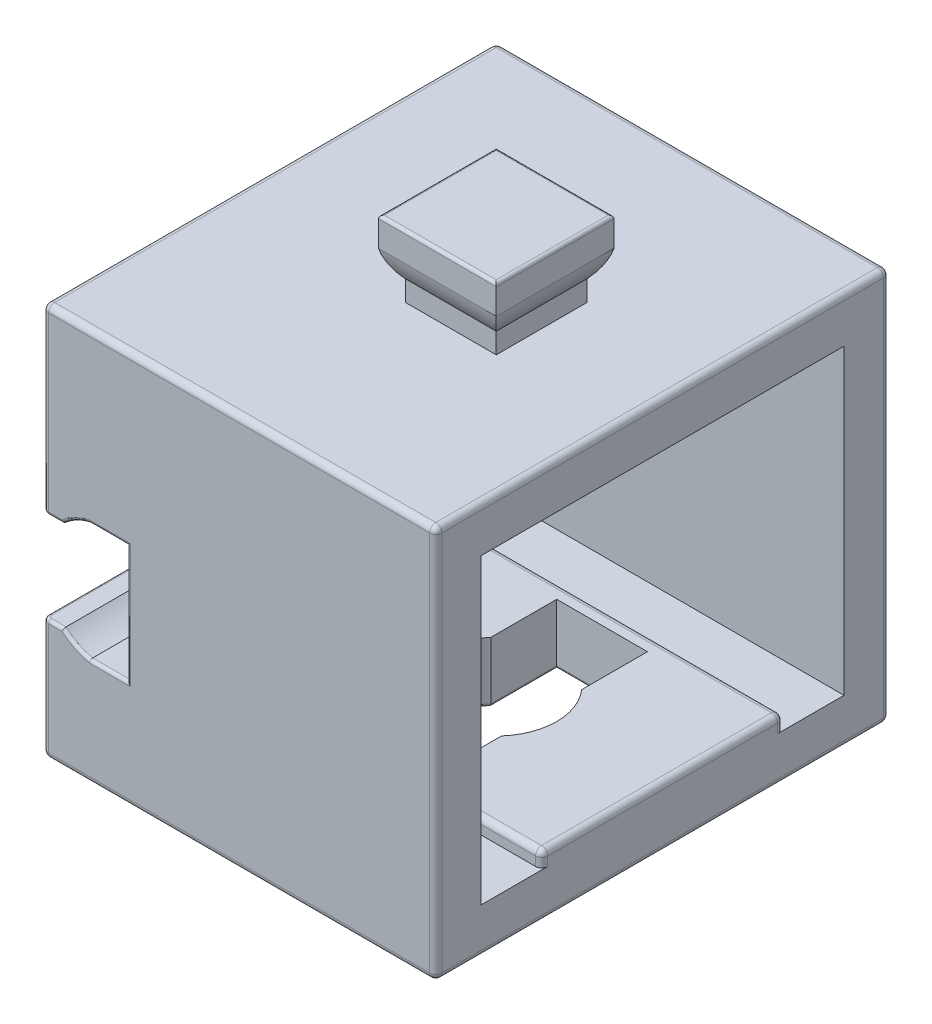
SolidWorks part; units mm, degrees
ref_plane "前视基准面" through (0, 0, 0) normal (0, 0, 1) x (1, 0, 0)
ref_plane "上视基准面" through (0, 0, 0) normal (0, 1, 0) x (1, 0, 0)
ref_plane "右视基准面" through (0, 0, 0) normal (1, 0, 0) x (0, 0, -1)
sketch "草图1" plane through (0, 0, 0) normal (0, 1, 0) x (1, 0, 0)
  line L0 (-6.5, 7.5) -> (-6.5, -7.5)
  line L1 (-6.5, 7.5) -> (6.5, 7.5)
  line L2 (-6.5, -7.5) -> (6.5, -7.5)
  line L3 (6.5, 7.5) -> (6.5, -7.5)
  line L4 (-6.5, 7.5) -> (6.5, -7.5) construction
  line L5 (-6.5, -7.5) -> (6.5, 7.5) construction
  point P1 (0, 0)
  dimension "D1" = 13
  dimension "D2" = 15
extrude "凸台-拉伸1" add sketch "草图1" along normal blind 13
sketch "草图2" plane through (6.5, 0, 0) normal (1, 0, 0) x (0, 0, -1)
  line L0 (-7.5, 13) -> (7.5, 13) construction
  line L1 (-6, 11.5) -> (6, 11.5)
  line L2 (-6, 11.5) -> (-6, 1.5)
  line L3 (-4, 1.5) -> (-6, 1.5)
  line L4 (6, 11.5) -> (6, 1.5)
  line L5 (-7.5, 13) -> (-7.5, 0) construction
  line L6 (7.5, 13) -> (7.5, 0) construction
  line L8 (-4, 2) -> (4, 2)
  line L9 (-4, 2) -> (-4, 1.5)
  line L10 (4, 1.5) -> (6, 1.5)
  line L11 (4, 2) -> (4, 1.5)
  dimension "D1" = 1.5
  dimension "D2" = 1.5
  dimension "D3" = 1.5
  dimension "D4" = 0.5
  dimension "D5" = 4
  dimension "D6" = 8
  dimension "D7" = 2
  dimension "D8" = 0.5
extrude "切除-拉伸1" cut sketch "草图2" against normal blind 11.5
sketch "草图3" plane through (-5, 0, 0) normal (1, 0, 0) x (0, 0, -1)
  line L0 (0, 0) -> (0, 5.5) construction
  line L1 (-7.5, 0) -> (7.5, 0) construction
  line L2 (0, 5.5) -> (-6, 5.5) construction
  line L3 (-6, 11.5) -> (-6, 1.5) construction
  line L4 (0, 5.5) -> (2.5, 5.5) construction
  line L5 (0, 8.5) -> (2.5, 8.5)
  line L6 (0, 8.5) -> (-6, 8.5)
  line L7 (0, 2.5) -> (2.5, 2.5)
  line L8 (0, 2.5) -> (-6, 2.5)
  line L9 (-6, 8.5) -> (-6, 2.5)
  line L10 (2.5, 8.5) -> (2.5, 2.5)
  dimension "D1" = 5.5
  dimension "D2" = 6
  dimension "D3" = 2.5
  dimension "D4" = 3
  dimension "D5" = 3
extrude "凸台-拉伸2" add sketch "草图3" along normal blind 1.5
sketch "草图4" plane through (0, 0, 0) normal (0, -1, 0) x (1, 0, 0)
  line L0 (6.5, 0) -> (1, 0) construction
  line L1 (6.5, 7.5) -> (6.5, -7.5) construction
  line L3 (2.5, 3.5) -> (-0.5, 3.5)
  line L4 (2.5, 3.5) -> (2.5, 1.3229)
  line L5 (-0.5, 3.5) -> (-0.5, 1.3229)
  line L6 (2.5, -3.5) -> (-0.5, -3.5)
  line L7 (2.5, 3.5) -> (-0.5, -3.5) construction
  line L8 (-0.5, 3.5) -> (2.5, -3.5) construction
  line L9 (-0.5, -1.3229) -> (-0.5, -3.5)
  line L10 (2.5, -1.3229) -> (2.5, -3.5)
  arc A0 (-0.5, 1.3229) -> (-0.5, -1.3229) centre (1, 0) ccw
  arc A1 (2.5, -1.3229) -> (2.5, 1.3229) centre (1, 0) ccw
  dimension "D2" = 4
  dimension "D1" = 5.5
  dimension "D3" = 3
  dimension "D4" = 7
extrude "切除-拉伸2" cut sketch "草图4" against normal up to next
sketch "草图5" plane through (0, 0, 7.5) normal (0, 0, 1) x (1, 0, 0)
  line L0 (-6.5, 13) -> (-6.5, 5.5) construction
  line L1 (-6.5, 13) -> (-6.5, 0) construction
  line L2 (-6.5, 5.5) -> (-4.5, 5.5) construction
  line L3 (-4.5, 5.5) -> (-3.7, 5.5) construction
  line L4 (-6.5, 4) -> (-6.5, 7)
  line L5 (-6.5, 7) -> (-5.8229, 7)
  line L6 (-3.7, 3.55) -> (-3.7, 7.45)
  line L7 (-3.7, 7.45) -> (-4.9444, 7.45)
  line L8 (-3.7, 3.55) -> (-4.9444, 3.55)
  line L9 (-6.5, 4) -> (-5.8229, 4)
  arc A0 (-4.9444, 7.45) -> (-5.8229, 7) centre (-4.5, 5.5) ccw
  arc A1 (-4.9444, 3.55) -> (-5.8229, 4) centre (-4.5, 5.5) cw
  dimension "D6" = 2
  dimension "D1" = 7.5
  dimension "D2" = 2
  dimension "D3" = 0.8
  dimension "D4" = 1.5
  dimension "D5" = 1.95
extrude "切除-拉伸3" cut sketch "草图5" against normal blind 9.5
sketch "草图6" plane through (0, 0, 0) normal (0, 0, 1) x (1, 0, 0)
  line L0 (-6.5, 13) -> (1, 13) construction
  line L1 (-6.5, 13) -> (6.5, 13) construction
  line L2 (1, 13) -> (1, 15) construction
  line L3 (1, 15) -> (1, 15.5) construction
  line L4 (-0.5, 13) -> (2.5, 13)
  line L5 (2.5, 13) -> (2.5, 13.6771)
  line L6 (-0.95, 15.5) -> (2.95, 15.5)
  line L7 (2.95, 15.5) -> (2.95, 14.5556)
  line L8 (-0.5, 13) -> (-0.5, 13.6771)
  line L9 (-0.95, 15.5) -> (-0.95, 14.5556)
  arc A0 (2.5, 13.6771) -> (2.95, 14.5556) centre (1, 15) ccw
  arc A1 (-0.5, 13.6771) -> (-0.95, 14.5556) centre (1, 15) cw
  dimension "D6" = 2
  dimension "D1" = 7.5
  dimension "D2" = 2
  dimension "D3" = 0.5
  dimension "D4" = 1.5
  dimension "D5" = 1.95
extrude "凸台-拉伸3" add sketch "草图6" along normal blind 2 and the other way blind 2
sketch "草图7" plane through (0, 0, 0) normal (1, 0, 0) x (0, 0, -1)
  line L0 (0, 13) -> (0, 15) construction
  line L1 (2, 13) -> (-2, 13) construction
  line L2 (0, 15) -> (0, 15.5) construction
  line L3 (2, 15.5) -> (-2, 15.5) construction
  line L4 (0, 13) -> (1.5, 13) construction
  line L5 (1.5, 13) -> (1.5, 13.6771)
  line L6 (0, 15.5) -> (1.95, 15.5) construction
  line L7 (1.95, 15.5) -> (1.95, 14.5556)
  line L8 (1.95, 15.5) -> (2, 15.5)
  line L9 (2, 15.5) -> (2, 13)
  line L10 (2, 13) -> (1.5, 13)
  line L11 (-2, 13) -> (-1.5, 13)
  line L12 (-1.5, 13) -> (-1.5, 13.6771)
  line L13 (-2, 15.5) -> (-2, 13)
  line L14 (-1.95, 15.5) -> (-1.95, 14.5556)
  line L15 (-1.95, 15.5) -> (-2, 15.5)
  arc A0 (1.5, 13.6771) -> (1.95, 14.5556) centre (0, 15) ccw
  arc A1 (-1.5, 13.6771) -> (-1.95, 14.5556) centre (0, 15) cw
  dimension "D4" = 2
  dimension "D1" = 2
  dimension "D2" = 1.5
  dimension "D3" = 1.95
extrude "切除-拉伸4" cut sketch "草图7" against normal blind 2 and the other way blind 4
fillet "圆角1" radius 0.2 13 edges at (0, 0, -7.5) (-6.5, 2, 7.5) (-6.5, 10, 7.5) (-6.5, 6.5, -7.5) (-6.5, 0, 0) (0, 0, 7.5) (0, 13, -7.5) (-6.5, 13, 0) (0, 13, 7.5) (6.5, 13, 0) (6.5, 6.5, -7.5) (6.5, 0, 0) (6.5, 6.5, 7.5)
fillet "圆角2" radius 0.2 8 edges at (-3.5, 8.5, 1.75) (-3.5, 2.5, 1.75) (-3.5, 5.5, -2.5) (0.75, 2, -4) (6.5, 1.75, -4) (6.5, 2, 0) (6.5, 1.75, 4) (0.75, 2, 4)
fillet "圆角3" radius 0.1 4 edges at (1, 15.5, 1.95) (-0.95, 15.5, 0) (1, 15.5, -1.95) (2.95, 15.5, 0)
fillet "圆角4" radius 0.1 11 edges at (-6.5, 7, 2.65) (-6.4414, 7, 7.4414) (-6.0614, 4, 7.5) (-6.4414, 4, 7.4414) (-6.0614, 7, 7.5) (-5.4118, 7.28, 7.5) (-4.3222, 7.45, 7.5) (-3.7, 5.5, 7.5) (-4.3222, 3.55, 7.5) (-5.4118, 3.72, 7.5) (-6.5, 4, 2.65)
fillet "圆角5" radius 0.1 8 edges at (2.5, 0, 2.4114) (3, 0, 0) (2.5, 0, -2.4114) (1, 0, -3.5) (-0.5, 0, -2.4114) (-1, 0, 0) (-0.5, 0, 2.4114) (1, 0, 3.5)
